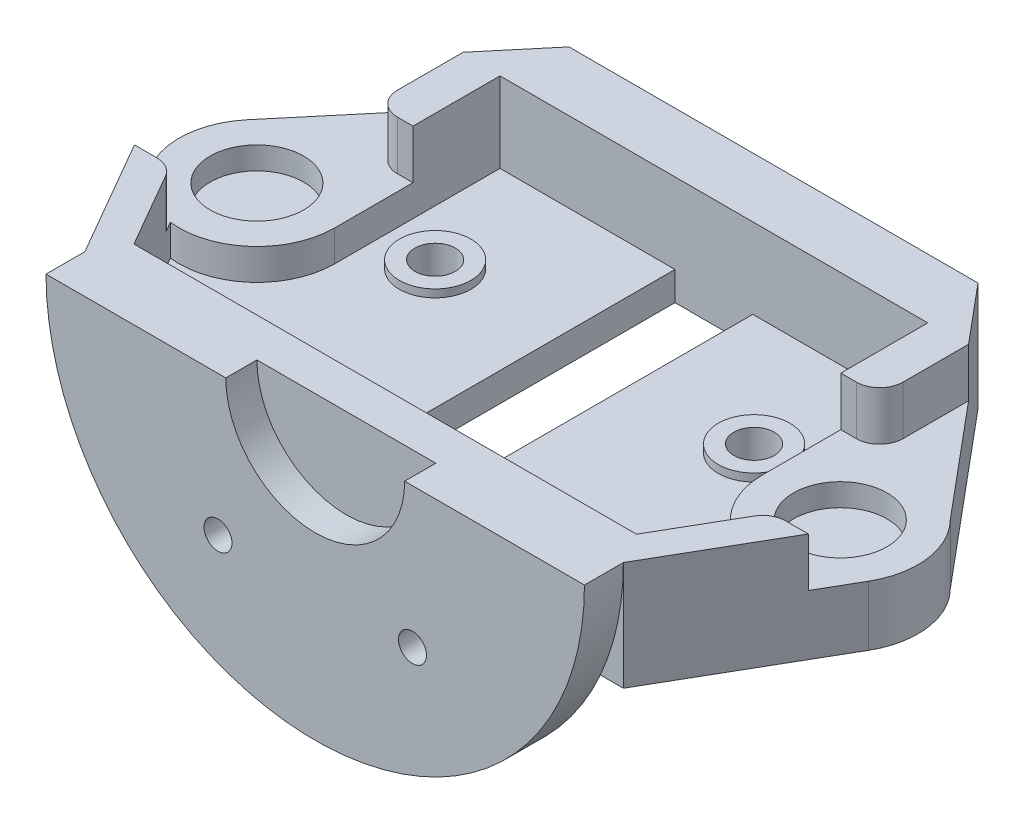
SolidWorks part; units mm, degrees
ref_plane "前视基准面" through (0, 0, 0) normal (0, 0, 1) x (1, 0, 0)
ref_plane "上视基准面" through (0, 0, 0) normal (0, 1, 0) x (1, 0, 0)
ref_plane "右视基准面" through (0, 0, 0) normal (1, 0, 0) x (0, 0, -1)
other "Configuration Table"
sketch "草图1" plane through (0, 0, 0) normal (0, 1, 0) x (1, 0, 0)
  line L0 (13.7094, 53.9161) -> (-5.1604, 31.4279)
  line L1 (0, 0) -> (80, 0) construction
  line L2 (0, 0) -> (0, 53.9161) construction
  line L3 (0, 53.9161) -> (80, 53.9161) construction
  line L5 (40, 23.4793) -> (40, -20571.3061) construction
  line L6 (19.5, 30.9161) -> (60.5, 30.9161) construction
  line L7 (2.5, 25) -> (77.5, 25) construction
  line L8 (2.5, 25) -> (19.5, 30.9161) construction
  line L9 (60.5, 30.9161) -> (77.5, 25) construction
  line L10 (0, 28.2261) -> (0, 0) construction
  line L11 (0, 0) -> (80, 0) construction
  line L12 (13.7094, 53.9161) -> (66.2906, 53.9161)
  line L13 (80, 28.2261) -> (80, 0) construction
  line L14 (66.2906, 53.9161) -> (84.5711, 32.0711)
  line L15 (-6.1603, 20) -> (5.3868, 0)
  line L17 (5.3868, 0) -> (74.6132, 0)
  line L18 (86.1603, 20) -> (74.6132, 0)
  circle A0 centre (2.5, 25) radius 6 construction
  circle A1 centre (19.5, 30.9161) radius 2.6 construction
  circle A2 centre (77.5, 25) radius 6 construction
  circle A3 centre (60.5, 30.9161) radius 2.6 construction
  arc A4 (-5.1604, 31.4279) -> (-6.1603, 20) centre (2.5, 25) ccw
  arc A5 (84.5711, 32.0711) -> (86.1603, 20) centre (77.5, 25) cw
  point P9 (40, 53.9161)
  point P12 (40, 30.9161)
  point P15 (40, 25)
  point P16 (40, 0)
  point P24 (40, 53.9161)
  point P28 (40, 0)
  point P29 (15.0203, 0)
  point P30 (20, 50)
  dimension "D4" = 12
  dimension "D5" = 5.2
  dimension "D10" = 20
  dimension "D2" = 75
  dimension "D3" = 18
  dimension "D6" = 50
  dimension "D7" = 80
  dimension "D8" = 25
  dimension "D9" = 23
  dimension "D11" = 60
  dimension "D12" = 41
extrude "凸台-拉伸1" add sketch "草图1" along normal blind 14 contours L17 L18 A5 L14 L12 L0 A4 L15
sketch "草图2" plane through (0, 14, 0) normal (0, 1, 0) x (1, 0, 0)
  line L0 (2.5, 25) -> (77.5, 25) construction
  line L1 (40, 25) -> (40, 50025) construction
  line L2 (19.9971, 29.2251) -> (60.0029, 29.2251) construction
  line L3 (19.9971, 29.2251) -> (2.5, 25) construction
  line L4 (1.3038, 15.0718) -> (7.6962, 4)
  line L5 (7.6962, 4) -> (72.3038, 4)
  line L6 (-6.1603, 20) -> (5.3868, 0)
  line L7 (5.3868, 0) -> (74.6132, 0)
  line L8 (74.6132, 0) -> (86.1603, 20)
  line L9 (84.5711, 32.0711) -> (66.2906, 53.9161)
  line L10 (66.2906, 53.9161) -> (13.7094, 53.9161)
  line L11 (13.7094, 53.9161) -> (-5.1604, 31.4279)
  line L12 (-6.1603, 20) -> (5.3868, 0)
  line L13 (5.3868, 0) -> (74.6132, 0)
  line L14 (74.6132, 0) -> (86.1603, 20)
  line L15 (84.5711, 32.0711) -> (66.2906, 53.9161)
  line L16 (66.2906, 53.9161) -> (13.7094, 53.9161)
  line L17 (13.7094, 53.9161) -> (-5.1604, 31.4279)
  line L22 (7.5, 46.516) -> (7.5, 35.0671)
  line L23 (7.5, 35.0671) -> (12.5, 35.0671)
  line L24 (12.5, 35.0671) -> (12.5, 46.2519)
  line L25 (-2.6962, 22) -> (7.6962, 4) construction
  line L26 (15.5746, 49.9161) -> (-2.0963, 28.8567) construction
  line L27 (1.3038, 15.0718) -> (-3.315, 15.0718)
  line L28 (12.5, 46.2519) -> (67.5, 46.2519)
  line L29 (72.3038, 4) -> (82.6962, 22) construction
  line L30 (7.6962, 4) -> (72.3038, 4) construction
  line L31 (72.5, 46.516) -> (69.411, 50.1872)
  line L32 (78.6962, 15.0718) -> (83.315, 15.0718)
  line L33 (67.5, 35.0671) -> (67.5, 46.2519)
  line L34 (81.6317, 29.3507) -> (64.4221, 49.9161) construction
  line L35 (64.4221, 49.9161) -> (15.5746, 49.9161) construction
  line L36 (72.5, 35.0671) -> (67.5, 35.0671)
  line L37 (72.5, 46.516) -> (72.5, 35.0671)
  line L39 (66.2906, 53.9161) -> (85.1604, 31.4279)
  line L40 (86.1603, 20) -> (74.6132, 0)
  line L41 (78.6962, 15.0718) -> (72.3038, 4)
  arc A2 (86.1603, 20) -> (84.5711, 32.0711) centre (77.5, 25) ccw
  arc A3 (-5.1604, 31.4279) -> (-6.1603, 20) centre (2.5, 25) ccw
  arc A4 (86.1603, 20) -> (84.5711, 32.0711) centre (77.5, 25) ccw
  arc A5 (-5.1604, 31.4279) -> (-6.1603, 20) centre (2.5, 25) ccw
  arc A6 (-2.0963, 28.8567) -> (-2.6962, 22) centre (2.5, 25) ccw construction
  circle A7 centre (2.5, 25) radius 10 construction
  arc A8 (82.6962, 22) -> (81.6317, 29.3507) centre (77.5, 25) ccw construction
  arc A9 (84.5711, 32.0711) -> (86.1603, 20) centre (77.5, 25) cw construction
  circle A10 centre (77.5, 25) radius 10 construction
  arc A11 (85.1604, 31.4279) -> (86.1603, 20) centre (77.5, 25) cw
  point P9 (40, 25)
  point P15 (40, 29.2251)
  point P32 (40, 46.2519)
  point P40 (40, 4)
  point P47 (40, 49.9161)
  line M23 (-6.1603, 20) -> (5.3868, 0)
  arc M26 (86.1603, 20) -> (84.5711, 32.0711) centre (77.5, 25) ccw
  line M27 (84.5711, 32.0711) -> (66.2906, 53.9161)
  arc M30 (-5.1604, 31.4279) -> (-6.1603, 20) centre (2.5, 25) ccw
  dimension "D5" = 5
  dimension "D3" = 18
  dimension "D6" = 5
  dimension "D1" = 0
  dimension "D4" = 4
extrude "切除-拉伸1" cut sketch "草图2" against normal blind 6.3 contours L41 L32 L14 L37 L36 L33 L28 L24 L23 L22 L17 L27 L4 L5 M26 M27 M30 M23 region at (39.9942, 14, -24.7624)
sketch "草图3" plane through (0, 7.7, 0) normal (0, 1, 0) x (1, 0, 0)
  line L0 (78.6962, 15.0718) -> (72.3038, 4)
  line L1 (40, 25) -> (40, 50025) construction
  line L2 (27, 30.9161) -> (53, 30.9161) construction
  line L3 (12.5, 35.0671) -> (12.5, 25)
  line L4 (67.5, 46.2519) -> (67.5, 35.0671)
  line L5 (67.5, 35.0671) -> (67.5, 25)
  line L16 (72.3038, 4) -> (78.6962, 15.0718)
  line L17 (78.6962, 15.0718) -> (83.315, 15.0718)
  line L18 (83.315, 15.0718) -> (86.1603, 20)
  line L19 (85.7068, 30.7139) -> (72.5, 46.4959)
  line L20 (72.5, 46.4959) -> (72.5, 35.0671)
  line L21 (72.5, 35.0671) -> (67.5, 35.0671)
  line L22 (67.5, 35.0671) -> (67.5, 46.2519)
  line L23 (67.5, 46.2519) -> (12.5, 46.2519)
  line L24 (12.5, 46.2519) -> (12.5, 35.0671)
  line L25 (12.5, 35.0671) -> (7.5, 35.0671)
  line L26 (7.5, 35.0671) -> (7.5, 46.516)
  line L27 (7.5, 46.516) -> (-5.1604, 31.4279)
  line L28 (-6.1603, 20) -> (-3.315, 15.0718)
  line L29 (-3.315, 15.0718) -> (1.3038, 15.0718)
  line L30 (1.3038, 15.0718) -> (7.6962, 4)
  line L31 (7.6962, 4) -> (72.3038, 4)
  line L47 (72.3038, 4) -> (78.6962, 15.0718)
  line L48 (78.6962, 15.0718) -> (83.315, 15.0718)
  line L49 (83.315, 15.0718) -> (86.1603, 20)
  line L50 (84.5711, 32.0711) -> (72.5, 46.4959)
  line L51 (72.5, 46.4959) -> (72.5, 35.0671)
  line L52 (72.5, 35.0671) -> (67.5, 35.0671)
  line L53 (67.5, 35.0671) -> (67.5, 46.2519)
  line L54 (67.5, 46.2519) -> (12.5, 46.2519)
  line L55 (12.5, 46.2519) -> (12.5, 35.0671)
  line L56 (12.5, 35.0671) -> (7.5, 35.0671)
  line L57 (7.5, 35.0671) -> (7.5, 46.516)
  line L58 (7.5, 46.516) -> (-5.1604, 31.4279)
  line L59 (-6.1603, 20) -> (-3.315, 15.0718)
  line L60 (-3.315, 15.0718) -> (1.3038, 15.0718)
  line L61 (1.3038, 15.0718) -> (7.6962, 4)
  line L62 (7.6962, 4) -> (72.3038, 4)
  line L70 (67.5, 46.2519) -> (12.5, 46.2519)
  line L71 (12.5, 46.2519) -> (12.5, 35.0671)
  line L77 (1.3038, 15.0718) -> (7.6962, 4)
  line L78 (7.6962, 4) -> (72.3038, 4)
  arc A1 (85.1604, 31.4279) -> (86.1603, 20) centre (77.5, 25) cw
  circle A7 centre (2.5, 25) radius 10
  arc A8 (85.1604, 31.4279) -> (86.1603, 20) centre (77.5, 25) cw
  arc A9 (86.1603, 20) -> (85.7068, 30.7139) centre (77.5, 25) ccw
  arc A10 (-5.1604, 31.4279) -> (-6.1603, 20) centre (2.5, 25) ccw
  arc A11 (-5.1604, 31.4279) -> (-6.1603, 20) centre (2.5, 25) ccw
  arc A12 (86.1603, 20) -> (84.5711, 32.0711) centre (77.5, 25) ccw
  arc A13 (-5.1604, 31.4279) -> (-6.1603, 20) centre (2.5, 25) ccw
  arc A15 (-5.1604, 31.4279) -> (-6.1603, 20) centre (2.5, 25) ccw
  circle A16 centre (77.5, 25) radius 10
  point P9 (-7.4619, 25.8716)
  point P15 (40, 30.9161)
  point P32 (40, 4)
  point P37 (40, 46.2519)
  point P38 (40, 6)
  point P40 (40, 46.2519)
  line M32 (67.5, 35.0671) -> (67.5, 46.2519)
  line M33 (67.5, 46.2519) -> (12.5, 46.2519)
  line M34 (12.5, 46.2519) -> (12.5, 35.0671)
  dimension "D2" = 0
  dimension "D1" = 0
extrude "切除-拉伸2" cut sketch "草图3" against normal blind 3 contours A16 M32 M33 M34 region at (40, 7.7, -23.9639)
sketch "草图4" plane through (0, 7.7, 0) normal (0, 1, 0) x (1, 0, 0)
  circle A0 centre (2.5, 25) radius 6.01
  circle A1 centre (77.5, 25) radius 6.01
  dimension "D1" = 12.02
  dimension "D2" = 12.02
extrude "切除-拉伸3" cut sketch "草图4" against normal blind 2.9
sketch "草图5" plane through (0, 4.7, 0) normal (0, 1, 0) x (1, 0, 0)
  line L0 (2.5, 25) -> (77.5, 25) construction
  line L1 (40, 25) -> (40, 50025) construction
  line L2 (19.5, 30.9161) -> (60.5, 30.9161) construction
  line L3 (19.5, 30.9161) -> (19.5, 25) construction
  circle A0 centre (77.5, 25) radius 6.01 construction
  circle A1 centre (2.5, 25) radius 6.01 construction
  circle A2 centre (77.5, 25) radius 6.01 construction
  circle A3 centre (2.5, 25) radius 6.01 construction
  circle A4 centre (19.5, 30.9161) radius 2.6
  circle A5 centre (60.5, 30.9161) radius 2.6
  point P8 (40, 25)
  point P11 (40, 30.9161)
  dimension "D2" = 5.2
  dimension "D3" = 5.2
  dimension "D1" = 18
  dimension "D4" = 17
extrude "切除-拉伸4" cut sketch "草图5" against normal up to next
sketch "草图6" plane through (0, 4.7, 0) normal (0, 1, 0) x (1, 0, 0)
  line L6 (72.3038, 4) -> (78.6962, 15.0718)
  line L7 (72.3038, 4) -> (78.6962, 15.0718)
  line L8 (67.5, 46.2519) -> (12.5, 46.2519)
  line L9 (67.5, 25) -> (67.5, 46.2519)
  line L10 (67.5, 25) -> (67.5, 46.2519)
  line L11 (1.3038, 15.0718) -> (7.6962, 4)
  line L14 (67.5, 46.2519) -> (12.5, 46.2519)
  line L18 (1.3038, 15.0718) -> (7.6962, 4)
  line L19 (7.6962, 4) -> (72.3038, 4)
  line L20 (7.6962, 4) -> (72.3038, 4)
  line L27 (12.5, 46.2519) -> (12.5, 25)
  line L28 (12.5, 46.2519) -> (12.5, 25)
  circle A0 centre (60.5, 30.9161) radius 2.6 construction
  circle A1 centre (19.5, 30.9161) radius 2.6 construction
  arc A2 (67.5, 25) -> (78.6962, 15.0718) centre (77.5, 25) ccw
  arc A3 (1.3038, 15.0718) -> (12.5, 25) centre (2.5, 25) ccw
  arc A4 (67.5, 25) -> (78.6962, 15.0718) centre (77.5, 25) ccw
  circle A6 centre (60.5, 30.9161) radius 2.6 construction
  circle A7 centre (19.5, 30.9161) radius 2.6 construction
  circle A8 centre (19.5, 30.9161) radius 4.6
  circle A9 centre (60.5, 30.9161) radius 4.6
  arc A12 (1.3038, 15.0718) -> (12.5, 25) centre (2.5, 25) ccw
  dimension "D1" = 0
  dimension "D2" = 2
extrude "切除-拉伸6" cut sketch "草图6" against normal blind 1
sketch "草图7" plane through (0, 0, 0) normal (0, 0, 1) x (1, 0, 0)
  line L2 (5.3868, 14) -> (74.6132, 14) construction
  line L3 (5.3868, 14) -> (74.6132, 14)
  arc A1 (5.3868, 14) -> (74.6132, 14) centre (40, 14) ccw
extrude "凸台-拉伸2" add sketch "草图7" along normal blind 5
sketch "草图8" plane through (0, 0, 5) normal (0, 0, 1) x (1, 0, 0)
  line L0 (74.6132, 14) -> (5.3868, 14) construction
  circle A0 centre (40, 14) radius 11.5
  dimension "D1" = 23
extrude "切除-拉伸7" cut sketch "草图8" against normal blind 4
sketch "草图9" plane through (0, 0, 0) normal (0, 0, -1) x (-1, 0, 0)
  line L0 (-40, 14) -> (-40, -49986) construction
  line L1 (-13.7094, 14) -> (-66.2906, 14) construction
  line L2 (-52.5, -4) -> (-27.5, -4) construction
  circle A0 centre (-52.5, -4) radius 1.8
  circle A1 centre (-27.5, -4) radius 1.8
  circle A2 centre (-40, 14) radius 14 construction
  point P4 (-40, 14)
  point P7 (-40, -4)
  dimension "D3" = 3.6
  dimension "D4" = 3.6
  dimension "D5" = 28
  dimension "D1" = 18
  dimension "D2" = 25
extrude "切除-拉伸8" cut sketch "草图9" against normal up to next
fillet "圆角1" radius 3 4 edges at (78.6962, 10.85, -15.0718) (1.3038, 10.85, -15.0718) (72.5, 10.85, -35.0671) (7.5, 10.85, -35.0671)
sketch "草图11" plane through (0, 3.7, 0) normal (0, 1, 0) x (1, 0, 0)
  line L0 (40, 46.2519) -> (40, -49953.7481) construction
  line L1 (12.5, 46.2519) -> (67.5, 46.2519) construction
  line L2 (7.6962, 4) -> (72.3038, 4) construction
  line L3 (35, 46.2519) -> (45, 46.2519)
  line L4 (35, 46.2519) -> (35, 4)
  line L5 (35, 4) -> (45, 4)
  line L6 (45, 46.2519) -> (45, 4)
  point P4 (40, 46.2519)
  point P9 (40, 46.2519)
  dimension "D1" = 10
extrude "切除-拉伸9" cut sketch "草图11" against normal up to next
